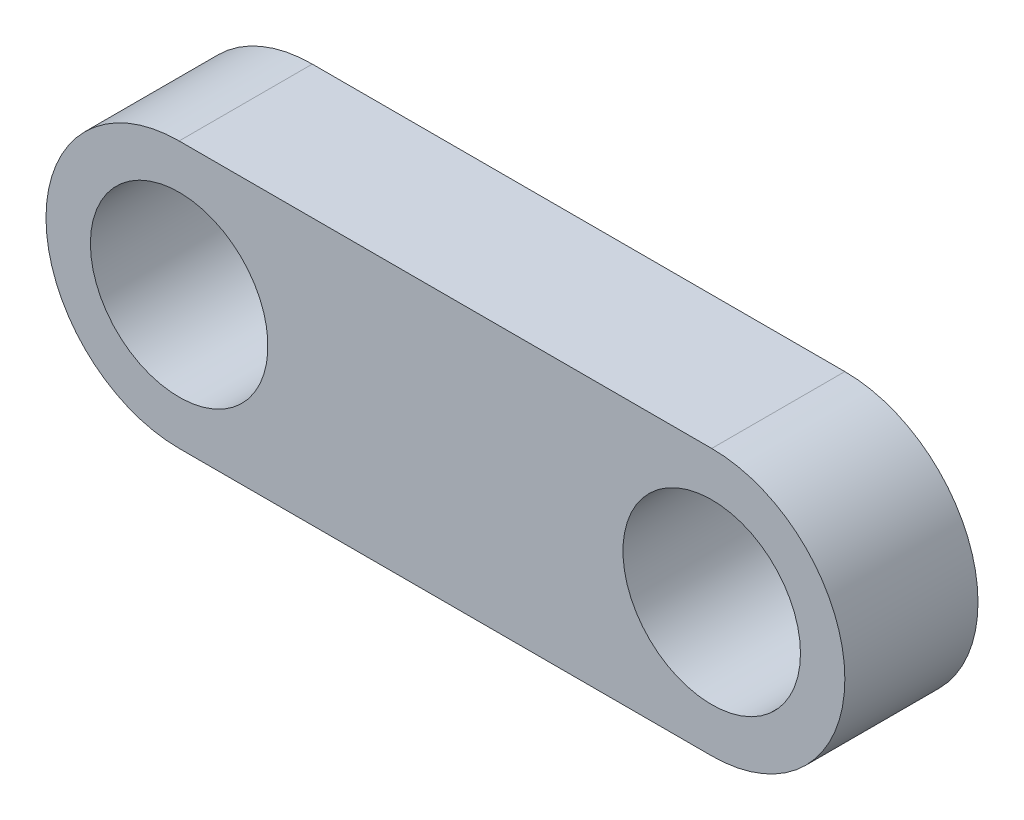
SolidWorks part; units mm, degrees
material "Stainless Steel (ferritic)"
ref_plane "Front Plane" through (0, 0, 0) normal (0, 0, 1) x (1, 0, 0)
ref_plane "Top Plane" through (0, 0, 0) normal (0, 1, 0) x (1, 0, 0)
ref_plane "Right Plane" through (0, 0, 0) normal (1, 0, 0) x (0, 0, -1)
sketch "Sketch1" plane through (0, 0, 0) normal (0, 0, 1) x (1, 0, 0)
  line L0 (0, 0) -> (-24, 0) construction
  line L7 (-12, 0) -> (-12, 6) construction
  line L8 (-24, 6) -> (0, 6)
  line L9 (-24, -6) -> (0, -6)
  circle A4 centre (0, 0) radius 4
  arc A5 (0, -6) -> (0, 6) centre (0, 0) ccw
  circle A6 centre (-24, 0) radius 4
  arc A7 (-24, -6) -> (-24, 6) centre (-24, 0) cw
  circle A9 centre (0, 0) radius 6 construction
  point P10 (6, 0)
  dimension "D1" = 8
  dimension "D2" = 2
  dimension "D3" = 24
extrude "Boss-Extrude1" add sketch "Sketch1" along normal blind 6
ref_axis "UnionHerrajeL" through (-24, 0, 6) along (0, 0, -1)
ref_axis "UnionHerrajeR" through (0, 0, 6) along (0, 0, -1)
